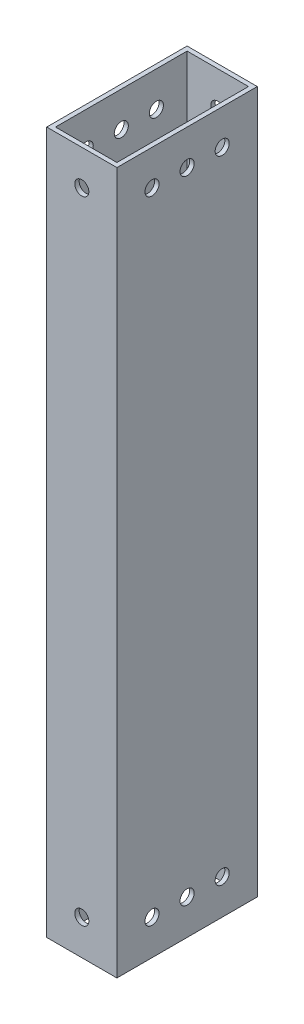
SolidWorks part; units mm, degrees
material "6061-T6 (SS)"
ref_plane "Front" through (0, 0, 0) normal (0, 0, 1) x (1, 0, 0)
ref_plane "Top" through (0, 0, 0) normal (0, 1, 0) x (1, 0, 0)
ref_plane "Right" through (0, 0, 0) normal (1, 0, 0) x (0, 0, -1)
sketch "Sketch1" plane through (0, 0, 0) normal (0, 1, 0) x (1, 0, 0)
  line L1 (12.7, 25.4) -> (-12.7, 25.4)
  line L2 (12.7, 25.4) -> (12.7, -25.4)
  line L3 (12.7, -25.4) -> (-12.7, -25.4)
  line L4 (-12.7, 25.4) -> (-12.7, -25.4)
  line L5 (12.7, 25.4) -> (-12.7, -25.4) construction
  line L6 (12.7, -25.4) -> (-12.7, 25.4) construction
  point P0 (0, 0)
  dimension "D1" = 25.4
  dimension "D2" = 50.8
extrude "Extrude-Thin1" add sketch "Sketch1" along normal up to surface (254 mm away) thin thin type one direction reverse wall 1.5875
sketch "Sketch4" plane through (-12.7, 0, 0) normal (-1, 0, 0) x (0, 0, 1)
  line L0 (-12.7, 12.7) -> (12.7, 12.7) construction
  line L3 (-12.7, 241.3) -> (12.7, 241.3) construction
  line L4 (-25.4, 0) -> (25.4, 0) construction
  line L5 (-25.4, 254) -> (25.4, 254) construction
  line L6 (-25.4, 254) -> (-25.4, 0) construction
  point P1 (-12.7, 12.7)
  point P2 (12.7, 12.7)
  point P6 (-12.7, 241.3)
  point P7 (12.7, 241.3)
  point P10 (0, 241.3)
  point P16 (-12.7, 241.3)
  point P18 (12.7, 241.3)
  point P22 (0, 12.7)
  point P26 (12.7, 12.7)
  point P28 (-12.7, 12.7)
  dimension "D1" = 12.7
  dimension "D2" = 12.7
  dimension "D3" = 12.7
hole_wizard "#10 Clearance Hole1" positions "Sketch4" profile "Sketch3" hole size "#10" standard "ANSI Inch" end condition through all
sketch "Sketch3" plane through (-12.7, 12.7, -12.7) normal (0, 1, 0) x (0, 0, 1)
  line L0 (0, 0) -> (0, 25.4)
  line L1 (0, 25.4) -> (2.5527, 25.4)
  line L2 (2.5527, 25.4) -> (2.5527, 0)
  line L5 (2.5527, 0) -> (0, 0)
  line L11 (0, -6.35) -> (0, 107.95) construction
  dimension "Thru Hole Dia." = 5.1054
  dimension "Thru Hole Depth" = 25.4
sketch "Sketch7" plane through (0, 0, 25.4) normal (0, 0, 1) x (1, 0, 0)
  line L0 (-12.7, 0) -> (12.7, 0) construction
  line L1 (-12.7, 254) -> (12.7, 254) construction
  point P0 (0, 12.7)
  point P2 (0, 241.3)
  dimension "D1" = 12.7
  dimension "D2" = 12.7
hole_wizard "#10 Clearance Hole2" positions "Sketch7" profile "Sketch6" hole size "#10" standard "ANSI Inch" end condition through all
sketch "Sketch6" plane through (0, 12.7, 25.4) normal (1, 0, 0) x (0, -1, 0)
  line L0 (0, 0) -> (0, 50.8)
  line L1 (0, 50.8) -> (2.5527, 50.8)
  line L2 (2.5527, 50.8) -> (2.5527, 0)
  line L5 (2.5527, 0) -> (0, 0)
  line L11 (0, -6.35) -> (0, 107.95) construction
  dimension "Thru Hole Dia." = 5.1054
  dimension "Thru Hole Depth" = 50.8
